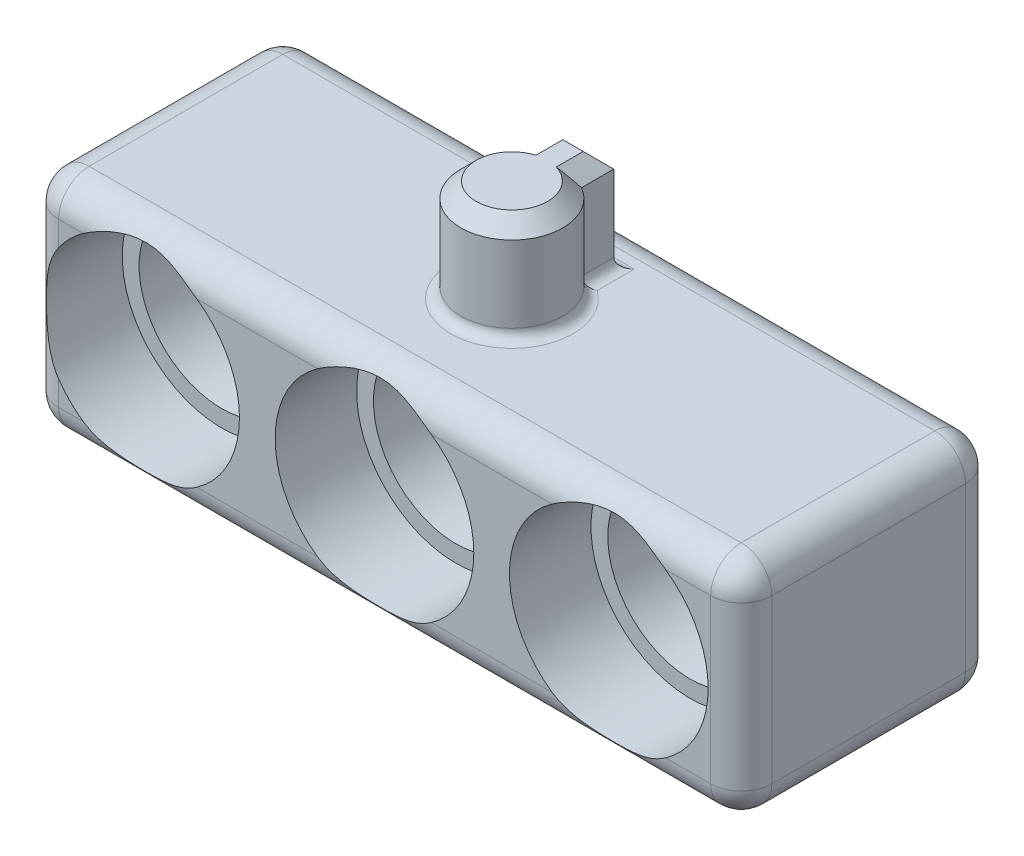
SolidWorks part; units mm, degrees
ref_plane "Alzado" through (0, 0, 0) normal (0, 0, 1) x (1, 0, 0)
ref_plane "Planta" through (0, 0, 0) normal (0, 1, 0) x (1, 0, 0)
ref_plane "Vista lateral" through (0, 0, 0) normal (1, 0, 0) x (0, 0, -1)
sketch "Sketch1" plane through (0, 0, 0) normal (0, 0, 1) x (1, 0, 0)
  line L0 (0, 0) -> (35, 0)
  line L1 (35, 0) -> (35, 22)
  line L2 (35, 22) -> (-35, 22)
  line L3 (-35, 22) -> (-35, 0)
  line L4 (-35, 0) -> (0, 0)
  point P5 (0, 0)
  point P7 (0, 0)
  point P8 (0, 0)
  dimension "D1" = 22
  dimension "D2" = 70
  dimension "D3" = 35
extrude "Boss-Extrude1" add sketch "Sketch1" along normal blind 25
sketch "Sketch2" plane through (0, 0, 25) normal (0, 0, 1) x (1, 0, 0)
  line L0 (-35, 0) -> (35, 0) construction
  line L1 (-35, 22) -> (-35, 0) construction
  circle A1 centre (-24, 11) radius 8.1
  point P1 (0, 11)
  point P2 (-17.9783, 11.1875)
  point P4 (-20.1033, 11.0625)
  point P5 (0, 0)
  dimension "D2" = 11
  dimension "D3" = 16.2
  dimension "D1" = 11
extrude "Cut-Extrude1" cut sketch "Sketch2" against normal through all and the other way through all contours A1
sketch "Sketch3" plane through (0, 0, 25) normal (0, 0, 1) x (1, 0, 0)
  line L0 (-35, 0) -> (35, 0) construction
  line L1 (-35, 22) -> (-35, 0) construction
  circle A0 centre (-24, 11) radius 9.75
  point P3 (0, 11)
  point P4 (0, 11)
  point P5 (-19.9783, 11)
  dimension "D1" = 19.5
  dimension "D2" = 11
  dimension "D3" = 11
extrude "Cut-Extrude2" cut sketch "Sketch3" against normal blind 8 contours A0
pattern_linear "LPattern1" count 3 spacing 23 along (1, 0, 0) of "Cut-Extrude2", "Cut-Extrude1"
fillet "Fillet2" radius 3 12 edges at (-35, 11, 25) (-35, 11, 0) (-35, 0, 12.5) (0, 0, 25) (0, 0, 0) (0, 22, 25) (-35, 22, 12.5) (0, 22, 0) (35, 0, 12.5) (35, 11, 25) (35, 22, 12.5) (35, 11, 0)
sketch "Sketch5" plane through (0, 22, 0) normal (0, 1, 0) x (1, 0, 0)
  line L0 (-0.0104, -12.5) -> (34.9896, -12.5) construction
  line L3 (-2.5104, -8.1699) -> (-2.5104, -5)
  line L4 (-0.0104, -12.5) -> (-35.0104, -12.5) construction
  line L5 (-2.5104, -5) -> (2.4896, -5)
  line L6 (2.4896, -8.1699) -> (2.4896, -5)
  arc A0 (-2.5104, -8.1699) -> (2.4896, -8.1699) centre (-0.0104, -12.5) ccw
  point P2 (-0.0104, -7.5)
  point P10 (0, 0)
  dimension "D2" = 10
  dimension "D1" = 12.5
  dimension "D3" = 35
  dimension "D4" = 35
  dimension "D5" = 5
extrude "Boss-Extrude2" add sketch "Sketch5" along normal blind 10
chamfer "Chamfer1" distance 1.5 angle 45 4 edges at (-0.0104, 32, 17.5) (-2.5104, 32, 6.5849) (-0.0104, 32, 5) (2.4896, 32, 6.5849)
fillet "Fillet3" radius 1 4 edges at (-0.0104, 22, 5) (-2.5104, 22, 6.5849) (2.4896, 22, 6.5849) (-0.0104, 22, 17.5)
